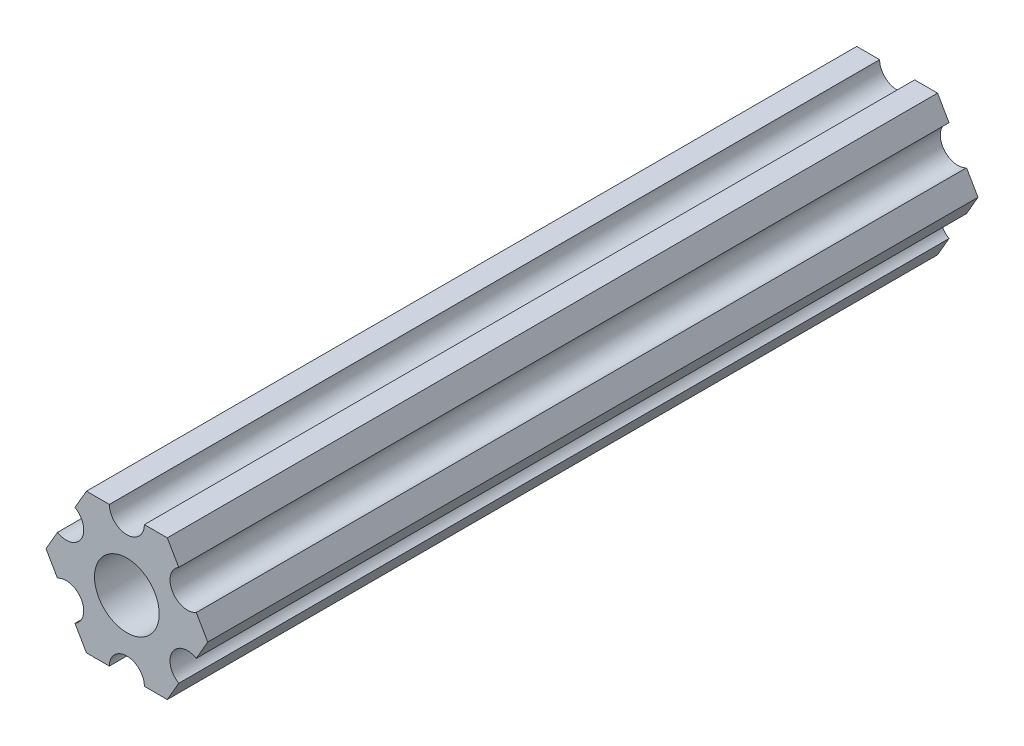
SolidWorks part; units mm, degrees
material "6061-T6 (SS)"
ref_plane "Front Plane" through (0, 0, 0) normal (0, 0, 1) x (1, 0, 0)
ref_plane "Top Plane" through (0, 0, 0) normal (0, 1, 0) x (1, 0, 0)
ref_plane "Right Plane" through (0, 0, 0) normal (1, 0, 0) x (0, 0, -1)
sketch "Sketch1" plane through (0, 0, 0) normal (0, 0, 1) x (1, 0, 0)
  line L0 (-4.7055, -4.5498) -> (-3.6662, -6.35)
  line L1 (-3.6662, -6.35) -> (-1.5875, -6.35)
  line L2 (1.5875, -6.35) -> (3.6662, -6.35)
  line L3 (3.6662, -6.35) -> (4.7055, -4.5498)
  line L4 (6.293, -1.8002) -> (7.3323, 0)
  line L5 (7.3323, 0) -> (6.293, 1.8002)
  line L6 (4.7055, 4.5498) -> (3.6662, 6.35)
  line L7 (3.6662, 6.35) -> (1.5875, 6.35)
  line L8 (-1.5875, 6.35) -> (-3.6662, 6.35)
  line L9 (-3.6662, 6.35) -> (-4.7055, 4.5498)
  line L10 (-6.293, 1.8002) -> (-7.3323, 0)
  line L11 (-7.3323, 0) -> (-6.293, -1.8002)
  circle A0 centre (0, 0) radius 2.9337
  arc A1 (-6.293, -1.8002) -> (-4.7055, -4.5498) centre (-5.4993, -3.175) cw
  arc A2 (-1.5875, -6.35) -> (1.5875, -6.35) centre (0, -6.35) cw
  arc A3 (4.7055, -4.5498) -> (6.293, -1.8002) centre (5.4993, -3.175) cw
  arc A4 (6.293, 1.8002) -> (4.7055, 4.5498) centre (5.4993, 3.175) cw
  arc A5 (1.5875, 6.35) -> (-1.5875, 6.35) centre (0, 6.35) cw
  arc A6 (-4.7055, 4.5498) -> (-6.293, 1.8002) centre (-5.4993, 3.175) cw
extrude "Boss-Extrude1" add sketch "Sketch1" against normal blind 69.85
